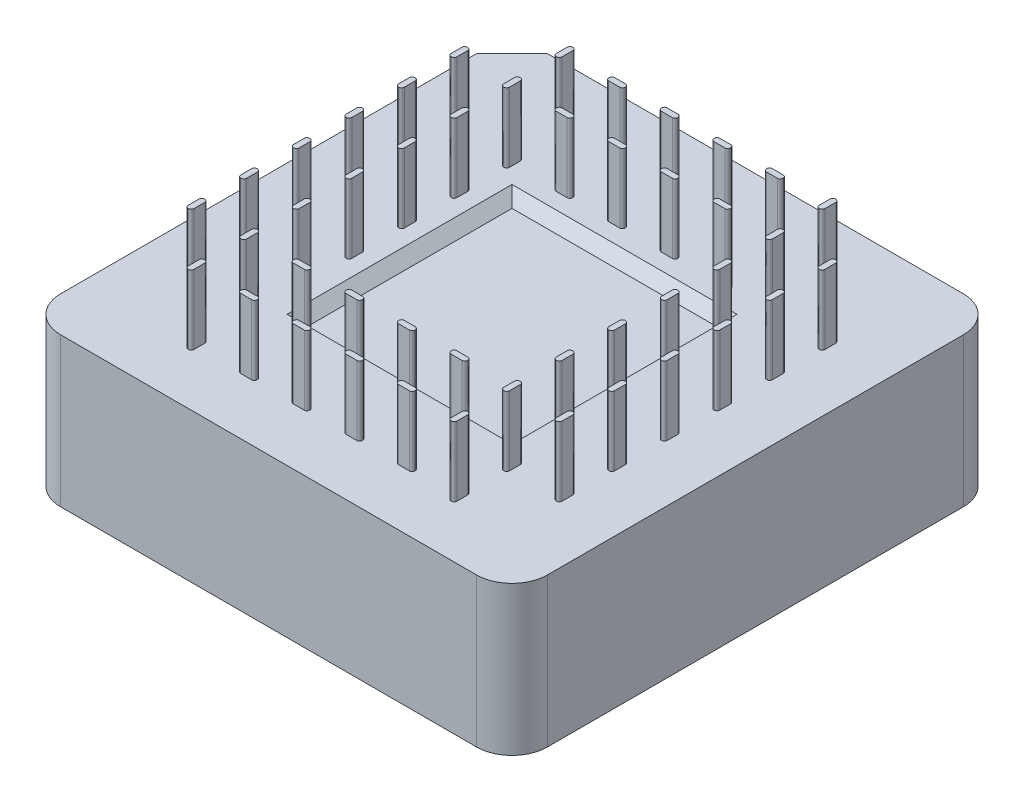
SolidWorks part; units mm, degrees
ref_plane "Alzado" through (0, 0, 0) normal (0, 0, 1) x (1, 0, 0)
ref_plane "pcb" through (0, 0, 0) normal (0, 1, 0) x (1, 0, 0)
ref_plane "Vista lateral" through (0, 0, 0) normal (1, 0, 0) x (0, 0, -1)
sketch "Croquis1" plane through (0, 0, 0) normal (0, 1, 0) x (1, 0, 0)
  line L0 (0, 0) -> (-6.35, 0) construction
  line L1 (-9.0297, -6.7437) -> (-8.7503, -5.9563) construction
  line L2 (-7.62, 0) -> (-8.89, 0) construction
  line L3 (-7.62, -7.62) -> (-7.62, -5.08) construction
  line L4 (-7.62, -7.62) -> (-8.89, -7.62) construction
  line L5 (-6.2103, -8.4963) -> (-6.4897, -9.2837) construction
  line L6 (-6.2103, -9.2837) -> (-6.4897, -8.4963) construction
  line L7 (-6.3432, -8.4963) -> (-6.3568, -8.4963)
  line L8 (-6.2103, -8.6292) -> (-6.2103, -9.1508)
  line L9 (-6.3432, -9.2837) -> (-6.3568, -9.2837)
  line L10 (-6.4897, -8.6292) -> (-6.4897, -9.1508)
  line L11 (-6.35, 6.35) -> (-7.62, 6.35) construction
  line L12 (-6.2103, 6.7437) -> (-6.4897, 5.9563) construction
  line L13 (-6.2103, 5.9563) -> (-6.4897, 6.7437) construction
  line L14 (-9.0297, 5.9563) -> (-8.7503, 6.7437) construction
  line L15 (-7.62, 5.08) -> (-8.89, 5.08) construction
  line L16 (-7.62, -2.54) -> (-8.89, -2.54) construction
  line L17 (-9.0297, -1.6637) -> (-8.7503, -0.8763) construction
  line L18 (-9.0297, -0.8763) -> (-8.7503, -1.6637) construction
  line L19 (-6.2103, -0.8763) -> (-6.4897, -1.6637) construction
  line L20 (-6.2103, -1.6637) -> (-6.4897, -0.8763) construction
  line L21 (-6.35, -1.27) -> (-7.62, -1.27) construction
  line L22 (-8.8968, -1.6637) -> (-8.8832, -1.6637)
  line L23 (-9.0297, -1.5308) -> (-9.0297, -1.0092)
  line L24 (-8.8968, -0.8763) -> (-8.8832, -0.8763)
  line L25 (-8.7503, -1.5308) -> (-8.7503, -1.0092)
  line L26 (-6.4897, -1.5308) -> (-6.4897, -1.0092)
  line L27 (-6.3432, -0.8763) -> (-6.3568, -0.8763)
  line L28 (-6.2103, -1.5308) -> (-6.2103, -1.0092)
  line L29 (-6.3432, -1.6637) -> (-6.3568, -1.6637)
  line L30 (-6.35, -3.81) -> (-7.62, -3.81) construction
  line L31 (-6.2103, -3.4163) -> (-6.4897, -4.2037) construction
  line L32 (-6.2103, -4.2037) -> (-6.4897, -3.4163) construction
  line L33 (-9.0297, -4.2037) -> (-8.7503, -3.4163) construction
  line L34 (-9.0297, -3.4163) -> (-8.7503, -4.2037) construction
  line L35 (-6.3432, -3.4163) -> (-6.3568, -3.4163)
  line L36 (-6.2103, -3.5492) -> (-6.2103, -4.0708)
  line L37 (-6.3432, -4.2037) -> (-6.3568, -4.2037)
  line L38 (-6.4897, -3.5492) -> (-6.4897, -4.0708)
  line L39 (-8.7503, -3.5492) -> (-8.7503, -4.0708)
  line L40 (-8.8968, -4.2037) -> (-8.8832, -4.2037)
  line L41 (-9.0297, -3.5492) -> (-9.0297, -4.0708)
  line L42 (-8.8968, -3.4163) -> (-8.8832, -3.4163)
  line L43 (-7.62, -5.08) -> (-8.89, -5.08) construction
  line L44 (-9.0297, -5.9563) -> (-8.7503, -6.7437) construction
  line L45 (-6.2103, -5.9563) -> (-6.4897, -6.7437) construction
  line L46 (-6.2103, -6.7437) -> (-6.4897, -5.9563) construction
  line L47 (-6.35, -6.35) -> (-7.62, -6.35) construction
  line L48 (-8.8968, -6.7437) -> (-8.8832, -6.7437)
  line L49 (-9.0297, -6.6108) -> (-9.0297, -6.0892)
  line L50 (-8.8968, -5.9563) -> (-8.8832, -5.9563)
  line L51 (-8.7503, -6.6108) -> (-8.7503, -6.0892)
  line L52 (-6.4897, -6.6108) -> (-6.4897, -6.0892)
  line L53 (-6.3432, -5.9563) -> (-6.3568, -5.9563)
  line L54 (-6.2103, -6.6108) -> (-6.2103, -6.0892)
  line L55 (-6.3432, -6.7437) -> (-6.3568, -6.7437)
  line L56 (-9.0297, 3.4163) -> (-8.7503, 4.2037) construction
  line L57 (-9.0297, 4.2037) -> (-8.7503, 3.4163) construction
  line L58 (-6.2103, 4.2037) -> (-6.4897, 3.4163) construction
  line L59 (-6.2103, 3.4163) -> (-6.4897, 4.2037) construction
  line L60 (-6.35, 3.81) -> (-7.62, 3.81) construction
  line L61 (-6.35, 1.27) -> (-7.62, 1.27) construction
  line L62 (-6.2103, 1.6637) -> (-6.4897, 0.8763) construction
  line L63 (-6.2103, 0.8763) -> (-6.4897, 1.6637) construction
  line L64 (-9.0297, 0.8763) -> (-8.7503, 1.6637) construction
  line L65 (-9.0297, 1.6637) -> (-8.7503, 0.8763) construction
  line L66 (-7.62, 2.54) -> (-8.89, 2.54) construction
  line L67 (-6.2103, 9.2837) -> (-6.4897, 8.4963) construction
  line L68 (-6.2103, 8.4963) -> (-6.4897, 9.2837) construction
  line L69 (-7.62, 7.62) -> (-8.89, 7.62) construction
  line L70 (-7.62, 7.62) -> (-7.62, 5.08) construction
  line L71 (-9.0297, 6.7437) -> (-8.7503, 5.9563) construction
  line L72 (-6.3432, 6.7437) -> (-6.3568, 6.7437)
  line L73 (-6.2103, 6.6108) -> (-6.2103, 6.0892)
  line L74 (-6.3432, 5.9563) -> (-6.3568, 5.9563)
  line L75 (-6.4897, 6.6108) -> (-6.4897, 6.0892)
  line L76 (-8.7503, 6.6108) -> (-8.7503, 6.0892)
  line L77 (-8.8968, 5.9563) -> (-8.8832, 5.9563)
  line L78 (-9.0297, 6.6108) -> (-9.0297, 6.0892)
  line L79 (-8.8968, 6.7437) -> (-8.8832, 6.7437)
  line L80 (-8.8968, 3.4163) -> (-8.8832, 3.4163)
  line L81 (-9.0297, 3.5492) -> (-9.0297, 4.0708)
  line L82 (-8.8968, 4.2037) -> (-8.8832, 4.2037)
  line L83 (-8.7503, 3.5492) -> (-8.7503, 4.0708)
  line L84 (-6.4897, 3.5492) -> (-6.4897, 4.0708)
  line L85 (-6.3432, 4.2037) -> (-6.3568, 4.2037)
  line L86 (-6.2103, 3.5492) -> (-6.2103, 4.0708)
  line L87 (-6.3432, 3.4163) -> (-6.3568, 3.4163)
  line L88 (-6.3432, 1.6637) -> (-6.3568, 1.6637)
  line L89 (-6.2103, 1.5308) -> (-6.2103, 1.0092)
  line L90 (-6.3432, 0.8763) -> (-6.3568, 0.8763)
  line L91 (-6.4897, 1.5308) -> (-6.4897, 1.0092)
  line L92 (-8.7503, 1.5308) -> (-8.7503, 1.0092)
  line L93 (-8.8968, 0.8763) -> (-8.8832, 0.8763)
  line L94 (-9.0297, 1.5308) -> (-9.0297, 1.0092)
  line L95 (-8.8968, 1.6637) -> (-8.8832, 1.6637)
  line L96 (-6.4897, 8.6292) -> (-6.4897, 9.1508)
  line L97 (-6.3432, 9.2837) -> (-6.3568, 9.2837)
  line L98 (-6.2103, 8.6292) -> (-6.2103, 9.1508)
  line L99 (-6.3432, 8.4963) -> (-6.3568, 8.4963)
  line L100 (9.0297, 6.7437) -> (8.7503, 5.9563) construction
  line L101 (7.62, 7.62) -> (7.62, 5.08) construction
  line L102 (7.62, 7.62) -> (8.89, 7.62) construction
  line L103 (6.2103, 8.4963) -> (6.4897, 9.2837) construction
  line L104 (6.2103, 9.2837) -> (6.4897, 8.4963) construction
  line L105 (7.62, 2.54) -> (8.89, 2.54) construction
  line L106 (9.0297, 1.6637) -> (8.7503, 0.8763) construction
  line L107 (9.0297, 0.8763) -> (8.7503, 1.6637) construction
  line L108 (6.2103, 0.8763) -> (6.4897, 1.6637) construction
  line L109 (6.2103, 1.6637) -> (6.4897, 0.8763) construction
  line L110 (6.35, 1.27) -> (7.62, 1.27) construction
  line L111 (6.35, 3.81) -> (7.62, 3.81) construction
  line L112 (6.2103, 3.4163) -> (6.4897, 4.2037) construction
  line L113 (6.2103, 4.2037) -> (6.4897, 3.4163) construction
  line L114 (9.0297, 4.2037) -> (8.7503, 3.4163) construction
  line L115 (9.0297, 3.4163) -> (8.7503, 4.2037) construction
  line L116 (6.35, -6.35) -> (7.62, -6.35) construction
  line L117 (6.2103, -6.7437) -> (6.4897, -5.9563) construction
  line L118 (6.2103, -5.9563) -> (6.4897, -6.7437) construction
  line L119 (9.0297, -5.9563) -> (8.7503, -6.7437) construction
  line L120 (7.62, -5.08) -> (8.89, -5.08) construction
  line L121 (9.0297, -3.4163) -> (8.7503, -4.2037) construction
  line L122 (9.0297, -4.2037) -> (8.7503, -3.4163) construction
  line L123 (6.2103, -4.2037) -> (6.4897, -3.4163) construction
  line L124 (6.2103, -3.4163) -> (6.4897, -4.2037) construction
  line L125 (6.35, -3.81) -> (7.62, -3.81) construction
  line L126 (6.35, -1.27) -> (7.62, -1.27) construction
  line L127 (6.2103, -1.6637) -> (6.4897, -0.8763) construction
  line L128 (6.2103, -0.8763) -> (6.4897, -1.6637) construction
  line L129 (9.0297, -0.8763) -> (8.7503, -1.6637) construction
  line L130 (9.0297, -1.6637) -> (8.7503, -0.8763) construction
  line L131 (7.62, -2.54) -> (8.89, -2.54) construction
  line L132 (7.62, 5.08) -> (8.89, 5.08) construction
  line L133 (9.0297, 5.9563) -> (8.7503, 6.7437) construction
  line L134 (6.2103, 5.9563) -> (6.4897, 6.7437) construction
  line L135 (6.2103, 6.7437) -> (6.4897, 5.9563) construction
  line L136 (6.35, 6.35) -> (7.62, 6.35) construction
  line L137 (6.2103, -9.2837) -> (6.4897, -8.4963) construction
  line L138 (6.2103, -8.4963) -> (6.4897, -9.2837) construction
  line L139 (7.62, -7.62) -> (8.89, -7.62) construction
  line L140 (7.62, -7.62) -> (7.62, -5.08) construction
  line L141 (7.62, 0) -> (8.89, 0) construction
  line L142 (9.0297, -6.7437) -> (8.7503, -5.9563) construction
  line L143 (6.3432, 8.4963) -> (6.3568, 8.4963)
  line L144 (6.2103, 8.6292) -> (6.2103, 9.1508)
  line L145 (6.3432, 9.2837) -> (6.3568, 9.2837)
  line L146 (6.4897, 8.6292) -> (6.4897, 9.1508)
  line L147 (8.8968, 1.6637) -> (8.8832, 1.6637)
  line L148 (9.0297, 1.5308) -> (9.0297, 1.0092)
  line L149 (8.8968, 0.8763) -> (8.8832, 0.8763)
  line L150 (8.7503, 1.5308) -> (8.7503, 1.0092)
  line L151 (6.4897, 1.5308) -> (6.4897, 1.0092)
  line L152 (6.3432, 0.8763) -> (6.3568, 0.8763)
  line L153 (6.2103, 1.5308) -> (6.2103, 1.0092)
  line L154 (6.3432, 1.6637) -> (6.3568, 1.6637)
  line L155 (6.3432, 3.4163) -> (6.3568, 3.4163)
  line L156 (6.2103, 3.5492) -> (6.2103, 4.0708)
  line L157 (0, 6.35) -> (0, -6.35) construction
  line L158 (6.3432, 4.2037) -> (6.3568, 4.2037)
  line L159 (6.4897, 3.5492) -> (6.4897, 4.0708)
  line L160 (8.7503, 3.5492) -> (8.7503, 4.0708)
  line L161 (8.8968, 4.2037) -> (8.8832, 4.2037)
  line L162 (9.0297, 3.5492) -> (9.0297, 4.0708)
  line L163 (8.8968, 3.4163) -> (8.8832, 3.4163)
  line L164 (8.8968, 6.7437) -> (8.8832, 6.7437)
  line L165 (9.0297, 6.6108) -> (9.0297, 6.0892)
  line L166 (8.8968, 5.9563) -> (8.8832, 5.9563)
  line L167 (8.7503, 6.6108) -> (8.7503, 6.0892)
  line L168 (6.4897, 6.6108) -> (6.4897, 6.0892)
  line L169 (6.3432, 5.9563) -> (6.3568, 5.9563)
  line L170 (6.2103, 6.6108) -> (6.2103, 6.0892)
  line L171 (6.3432, 6.7437) -> (6.3568, 6.7437)
  line L172 (6.3432, -6.7437) -> (6.3568, -6.7437)
  line L173 (6.2103, -6.6108) -> (6.2103, -6.0892)
  line L174 (6.3432, -5.9563) -> (6.3568, -5.9563)
  line L175 (6.4897, -6.6108) -> (6.4897, -6.0892)
  line L176 (8.7503, -6.6108) -> (8.7503, -6.0892)
  line L177 (8.8968, -5.9563) -> (8.8832, -5.9563)
  line L178 (9.0297, -6.6108) -> (9.0297, -6.0892)
  line L179 (8.8968, -6.7437) -> (8.8832, -6.7437)
  line L180 (8.8968, -3.4163) -> (8.8832, -3.4163)
  line L181 (9.0297, -3.5492) -> (9.0297, -4.0708)
  line L182 (8.8968, -4.2037) -> (8.8832, -4.2037)
  line L183 (8.7503, -3.5492) -> (8.7503, -4.0708)
  line L184 (6.4897, -3.5492) -> (6.4897, -4.0708)
  line L185 (6.3432, -4.2037) -> (6.3568, -4.2037)
  line L186 (6.2103, -3.5492) -> (6.2103, -4.0708)
  line L187 (6.3432, -3.4163) -> (6.3568, -3.4163)
  line L188 (6.3432, -1.6637) -> (6.3568, -1.6637)
  line L189 (6.2103, -1.5308) -> (6.2103, -1.0092)
  line L190 (6.3432, -0.8763) -> (6.3568, -0.8763)
  line L191 (6.4897, -1.5308) -> (6.4897, -1.0092)
  line L192 (8.7503, -1.5308) -> (8.7503, -1.0092)
  line L193 (8.8968, -0.8763) -> (8.8832, -0.8763)
  line L194 (9.0297, -1.5308) -> (9.0297, -1.0092)
  line L195 (8.8968, -1.6637) -> (8.8832, -1.6637)
  line L196 (6.4897, -8.6292) -> (6.4897, -9.1508)
  line L197 (6.3432, -9.2837) -> (6.3568, -9.2837)
  line L198 (6.2103, -8.6292) -> (6.2103, -9.1508)
  line L199 (6.3432, -8.4963) -> (6.3568, -8.4963)
  line L200 (-6.35, -6.35) -> (-5.08, -6.35) construction
  line L201 (-5.08, -6.35) -> (-5.08, -5.08) construction
  line L202 (-5.08, -6.35) -> (-3.81, -6.35) construction
  line L203 (-3.81, -6.35) -> (-2.54, -6.35) construction
  line L204 (-3.5426, -6.2103) -> (-4.0774, -6.2103)
  line L205 (-3.4163, -6.3366) -> (-3.4163, -6.3634)
  line L206 (-3.5426, -6.4897) -> (-4.0774, -6.4897)
  line L207 (-4.2037, -6.3366) -> (-4.2037, -6.3634)
  line L208 (-3.4163, -6.2103) -> (-4.2037, -6.4897) construction
  line L209 (-3.4163, -6.4897) -> (-4.2037, -6.2103) construction
  line L210 (-2.54, -6.35) -> (-2.54, -5.08) construction
  line L211 (-1.6637, -6.4897) -> (-0.8763, -6.2103) construction
  line L212 (-1.6637, -6.2103) -> (-0.8763, -6.4897) construction
  line L213 (-0.8763, -6.3366) -> (-0.8763, -6.3634)
  line L214 (-1.5374, -6.4897) -> (-1.0026, -6.4897)
  line L215 (-1.6637, -6.3366) -> (-1.6637, -6.3634)
  line L216 (-1.5374, -6.2103) -> (-1.0026, -6.2103)
  line L217 (1.6637, -6.2103) -> (0.8763, -6.4897) construction
  line L218 (1.6637, -6.4897) -> (0.8763, -6.2103) construction
  line L219 (3.4163, -6.4897) -> (4.2037, -6.2103) construction
  line L220 (3.4163, -6.2103) -> (4.2037, -6.4897) construction
  line L221 (3.81, -6.35) -> (2.54, -6.35) construction
  line L222 (1.5374, -6.2103) -> (1.0026, -6.2103)
  line L223 (1.6637, -6.3366) -> (1.6637, -6.3634)
  line L224 (1.5374, -6.4897) -> (1.0026, -6.4897)
  line L225 (0.8763, -6.3366) -> (0.8763, -6.3634)
  line L226 (4.2037, -6.3366) -> (4.2037, -6.3634)
  line L227 (3.5426, -6.4897) -> (4.0774, -6.4897)
  line L228 (3.4163, -6.3366) -> (3.4163, -6.3634)
  line L229 (3.5426, -6.2103) -> (4.0774, -6.2103)
  line L230 (-2.54, -6.35) -> (-2.54, -7.62) construction
  line L231 (-2.54, -7.62) -> (-3.81, -7.62) construction
  line L232 (3.81, -8.89) -> (2.54, -8.89) construction
  line L233 (3.4163, -9.0297) -> (4.2037, -8.7503) construction
  line L234 (3.4163, -8.7503) -> (4.2037, -9.0297) construction
  line L235 (1.6637, -8.7503) -> (0.8763, -9.0297) construction
  line L236 (1.6637, -9.0297) -> (0.8763, -8.7503) construction
  line L237 (-1.6637, -9.0297) -> (-0.8763, -8.7503) construction
  line L238 (-1.6637, -8.7503) -> (-0.8763, -9.0297) construction
  line L239 (-3.4163, -8.7503) -> (-4.2037, -9.0297) construction
  line L240 (-3.4163, -9.0297) -> (-4.2037, -8.7503) construction
  line L241 (-3.81, -8.89) -> (-2.54, -8.89) construction
  line L242 (3.5426, -9.0297) -> (4.0774, -9.0297)
  line L243 (3.4163, -8.9034) -> (3.4163, -8.8766)
  line L244 (3.5426, -8.7503) -> (4.0774, -8.7503)
  line L245 (4.2037, -8.9034) -> (4.2037, -8.8766)
  line L246 (0.8763, -8.9034) -> (0.8763, -8.8766)
  line L247 (1.5374, -8.7503) -> (1.0026, -8.7503)
  line L248 (1.6637, -8.9034) -> (1.6637, -8.8766)
  line L249 (1.5374, -9.0297) -> (1.0026, -9.0297)
  line L250 (-1.5374, -9.0297) -> (-1.0026, -9.0297)
  line L251 (-1.6637, -8.9034) -> (-1.6637, -8.8766)
  line L252 (-1.5374, -8.7503) -> (-1.0026, -8.7503)
  line L253 (-0.8763, -8.9034) -> (-0.8763, -8.8766)
  line L254 (-4.2037, -8.9034) -> (-4.2037, -8.8766)
  line L255 (-3.5426, -8.7503) -> (-4.0774, -8.7503)
  line L256 (-3.4163, -8.9034) -> (-3.4163, -8.8766)
  line L257 (-3.5426, -9.0297) -> (-4.0774, -9.0297)
  line L258 (-3.81, 8.89) -> (-2.54, 8.89) construction
  line L259 (-3.4163, 9.0297) -> (-4.2037, 8.7503) construction
  line L260 (-3.4163, 8.7503) -> (-4.2037, 9.0297) construction
  line L261 (-1.6637, 8.7503) -> (-0.8763, 9.0297) construction
  line L262 (-1.6637, 9.0297) -> (-0.8763, 8.7503) construction
  line L263 (1.6637, 9.0297) -> (0.8763, 8.7503) construction
  line L264 (1.6637, 8.7503) -> (0.8763, 9.0297) construction
  line L265 (3.4163, 8.7503) -> (4.2037, 9.0297) construction
  line L266 (3.4163, 9.0297) -> (4.2037, 8.7503) construction
  line L267 (3.81, 8.89) -> (2.54, 8.89) construction
  line L268 (-2.54, 7.62) -> (-3.81, 7.62) construction
  line L269 (-2.54, 6.35) -> (-2.54, 7.62) construction
  line L270 (3.81, 6.35) -> (2.54, 6.35) construction
  line L271 (3.4163, 6.2103) -> (4.2037, 6.4897) construction
  line L272 (3.4163, 6.4897) -> (4.2037, 6.2103) construction
  line L273 (1.6637, 6.4897) -> (0.8763, 6.2103) construction
  line L274 (1.6637, 6.2103) -> (0.8763, 6.4897) construction
  line L275 (-1.6637, 6.2103) -> (-0.8763, 6.4897) construction
  line L276 (-1.6637, 6.4897) -> (-0.8763, 6.2103) construction
  line L277 (-2.54, 6.35) -> (-2.54, 5.08) construction
  line L278 (-3.4163, 6.4897) -> (-4.2037, 6.2103) construction
  line L279 (-3.4163, 6.2103) -> (-4.2037, 6.4897) construction
  line L280 (-3.81, 6.35) -> (-2.54, 6.35) construction
  line L281 (-5.08, 6.35) -> (-3.81, 6.35) construction
  line L282 (-3.5426, 9.0297) -> (-4.0774, 9.0297)
  line L283 (-3.4163, 8.9034) -> (-3.4163, 8.8766)
  line L284 (-3.5426, 8.7503) -> (-4.0774, 8.7503)
  line L285 (-4.2037, 8.9034) -> (-4.2037, 8.8766)
  line L286 (-0.8763, 8.9034) -> (-0.8763, 8.8766)
  line L287 (-1.5374, 8.7503) -> (-1.0026, 8.7503)
  line L288 (-1.6637, 8.9034) -> (-1.6637, 8.8766)
  line L289 (-1.5374, 9.0297) -> (-1.0026, 9.0297)
  line L290 (1.5374, 9.0297) -> (1.0026, 9.0297)
  line L291 (1.6637, 8.9034) -> (1.6637, 8.8766)
  line L292 (1.5374, 8.7503) -> (1.0026, 8.7503)
  line L293 (0.8763, 8.9034) -> (0.8763, 8.8766)
  line L294 (4.2037, 8.9034) -> (4.2037, 8.8766)
  line L295 (3.5426, 8.7503) -> (4.0774, 8.7503)
  line L296 (3.4163, 8.9034) -> (3.4163, 8.8766)
  line L297 (3.5426, 9.0297) -> (4.0774, 9.0297)
  line L298 (3.5426, 6.2103) -> (4.0774, 6.2103)
  line L299 (3.4163, 6.3366) -> (3.4163, 6.3634)
  line L300 (3.5426, 6.4897) -> (4.0774, 6.4897)
  line L301 (4.2037, 6.3366) -> (4.2037, 6.3634)
  line L302 (0.8763, 6.3366) -> (0.8763, 6.3634)
  line L303 (1.5374, 6.4897) -> (1.0026, 6.4897)
  line L304 (1.6637, 6.3366) -> (1.6637, 6.3634)
  line L305 (1.5374, 6.2103) -> (1.0026, 6.2103)
  line L306 (-1.5374, 6.2103) -> (-1.0026, 6.2103)
  line L307 (-1.6637, 6.3366) -> (-1.6637, 6.3634)
  line L308 (-1.5374, 6.4897) -> (-1.0026, 6.4897)
  line L309 (-0.8763, 6.3366) -> (-0.8763, 6.3634)
  line L310 (-4.2037, 6.3366) -> (-4.2037, 6.3634)
  line L311 (-3.5426, 6.4897) -> (-4.0774, 6.4897)
  line L312 (-3.4163, 6.3366) -> (-3.4163, 6.3634)
  line L313 (-3.5426, 6.2103) -> (-4.0774, 6.2103)
  arc A0 (-6.3432, -9.2837) -> (-6.2103, -9.1508) centre (-6.3432, -9.1508) ccw
  arc A1 (-6.3568, -9.2837) -> (-6.4897, -9.1508) centre (-6.3568, -9.1508) cw
  arc A2 (-6.2103, -8.6292) -> (-6.3432, -8.4963) centre (-6.3432, -8.6292) ccw
  arc A3 (-6.3568, -8.4963) -> (-6.4897, -8.6292) centre (-6.3568, -8.6292) ccw
  arc A4 (-6.3432, 5.9563) -> (-6.2103, 6.0892) centre (-6.3432, 6.0892) ccw
  arc A5 (-6.3568, 5.9563) -> (-6.4897, 6.0892) centre (-6.3568, 6.0892) cw
  arc A6 (-6.2103, 6.6108) -> (-6.3432, 6.7437) centre (-6.3432, 6.6108) ccw
  arc A7 (-6.3568, 6.7437) -> (-6.4897, 6.6108) centre (-6.3568, 6.6108) ccw
  arc A8 (-8.8968, -0.8763) -> (-9.0297, -1.0092) centre (-8.8968, -1.0092) ccw
  arc A9 (-8.8832, -0.8763) -> (-8.7503, -1.0092) centre (-8.8832, -1.0092) cw
  arc A10 (-9.0297, -1.5308) -> (-8.8968, -1.6637) centre (-8.8968, -1.5308) ccw
  arc A11 (-8.8832, -1.6637) -> (-8.7503, -1.5308) centre (-8.8832, -1.5308) ccw
  arc A12 (-6.3568, -1.6637) -> (-6.4897, -1.5308) centre (-6.3568, -1.5308) cw
  arc A13 (-6.2103, -1.5308) -> (-6.3432, -1.6637) centre (-6.3432, -1.5308) cw
  arc A14 (-6.3568, -0.8763) -> (-6.4897, -1.0092) centre (-6.3568, -1.0092) ccw
  arc A15 (-6.3432, -0.8763) -> (-6.2103, -1.0092) centre (-6.3432, -1.0092) cw
  arc A16 (-6.3432, -4.2037) -> (-6.2103, -4.0708) centre (-6.3432, -4.0708) ccw
  arc A17 (-6.3568, -4.2037) -> (-6.4897, -4.0708) centre (-6.3568, -4.0708) cw
  arc A18 (-6.2103, -3.5492) -> (-6.3432, -3.4163) centre (-6.3432, -3.5492) ccw
  arc A19 (-6.3568, -3.4163) -> (-6.4897, -3.5492) centre (-6.3568, -3.5492) ccw
  arc A20 (-8.8832, -3.4163) -> (-8.7503, -3.5492) centre (-8.8832, -3.5492) cw
  arc A21 (-9.0297, -3.5492) -> (-8.8968, -3.4163) centre (-8.8968, -3.5492) cw
  arc A22 (-8.8832, -4.2037) -> (-8.7503, -4.0708) centre (-8.8832, -4.0708) ccw
  arc A23 (-8.8968, -4.2037) -> (-9.0297, -4.0708) centre (-8.8968, -4.0708) cw
  arc A24 (-8.8968, -5.9563) -> (-9.0297, -6.0892) centre (-8.8968, -6.0892) ccw
  arc A25 (-8.8832, -5.9563) -> (-8.7503, -6.0892) centre (-8.8832, -6.0892) cw
  arc A26 (-9.0297, -6.6108) -> (-8.8968, -6.7437) centre (-8.8968, -6.6108) ccw
  arc A27 (-8.8832, -6.7437) -> (-8.7503, -6.6108) centre (-8.8832, -6.6108) ccw
  arc A28 (-6.3568, -6.7437) -> (-6.4897, -6.6108) centre (-6.3568, -6.6108) cw
  arc A29 (-6.2103, -6.6108) -> (-6.3432, -6.7437) centre (-6.3432, -6.6108) cw
  arc A30 (-6.3568, -5.9563) -> (-6.4897, -6.0892) centre (-6.3568, -6.0892) ccw
  arc A31 (-6.3432, -5.9563) -> (-6.2103, -6.0892) centre (-6.3432, -6.0892) cw
  arc A32 (-8.8832, 6.7437) -> (-8.7503, 6.6108) centre (-8.8832, 6.6108) cw
  arc A33 (-9.0297, 6.6108) -> (-8.8968, 6.7437) centre (-8.8968, 6.6108) cw
  arc A34 (-8.8832, 5.9563) -> (-8.7503, 6.0892) centre (-8.8832, 6.0892) ccw
  arc A35 (-8.8968, 5.9563) -> (-9.0297, 6.0892) centre (-8.8968, 6.0892) cw
  arc A36 (-8.8968, 4.2037) -> (-9.0297, 4.0708) centre (-8.8968, 4.0708) ccw
  arc A37 (-8.8832, 4.2037) -> (-8.7503, 4.0708) centre (-8.8832, 4.0708) cw
  arc A38 (-9.0297, 3.5492) -> (-8.8968, 3.4163) centre (-8.8968, 3.5492) ccw
  arc A39 (-8.8832, 3.4163) -> (-8.7503, 3.5492) centre (-8.8832, 3.5492) ccw
  arc A40 (-6.3568, 3.4163) -> (-6.4897, 3.5492) centre (-6.3568, 3.5492) cw
  arc A41 (-6.2103, 3.5492) -> (-6.3432, 3.4163) centre (-6.3432, 3.5492) cw
  arc A42 (-6.3568, 4.2037) -> (-6.4897, 4.0708) centre (-6.3568, 4.0708) ccw
  arc A43 (-6.3432, 4.2037) -> (-6.2103, 4.0708) centre (-6.3432, 4.0708) cw
  arc A44 (-6.3432, 0.8763) -> (-6.2103, 1.0092) centre (-6.3432, 1.0092) ccw
  arc A45 (-6.3568, 0.8763) -> (-6.4897, 1.0092) centre (-6.3568, 1.0092) cw
  arc A46 (-6.2103, 1.5308) -> (-6.3432, 1.6637) centre (-6.3432, 1.5308) ccw
  arc A47 (-6.3568, 1.6637) -> (-6.4897, 1.5308) centre (-6.3568, 1.5308) ccw
  arc A48 (-8.8832, 1.6637) -> (-8.7503, 1.5308) centre (-8.8832, 1.5308) cw
  arc A49 (-9.0297, 1.5308) -> (-8.8968, 1.6637) centre (-8.8968, 1.5308) cw
  arc A50 (-8.8832, 0.8763) -> (-8.7503, 1.0092) centre (-8.8832, 1.0092) ccw
  arc A51 (-8.8968, 0.8763) -> (-9.0297, 1.0092) centre (-8.8968, 1.0092) cw
  arc A52 (-6.3568, 8.4963) -> (-6.4897, 8.6292) centre (-6.3568, 8.6292) cw
  arc A53 (-6.2103, 8.6292) -> (-6.3432, 8.4963) centre (-6.3432, 8.6292) cw
  arc A54 (-6.3568, 9.2837) -> (-6.4897, 9.1508) centre (-6.3568, 9.1508) ccw
  arc A55 (-6.3432, 9.2837) -> (-6.2103, 9.1508) centre (-6.3432, 9.1508) cw
  arc A56 (6.3432, 9.2837) -> (6.2103, 9.1508) centre (6.3432, 9.1508) ccw
  arc A57 (6.3568, 9.2837) -> (6.4897, 9.1508) centre (6.3568, 9.1508) cw
  arc A58 (6.2103, 8.6292) -> (6.3432, 8.4963) centre (6.3432, 8.6292) ccw
  arc A59 (6.3568, 8.4963) -> (6.4897, 8.6292) centre (6.3568, 8.6292) ccw
  arc A60 (8.8968, 0.8763) -> (9.0297, 1.0092) centre (8.8968, 1.0092) ccw
  arc A61 (8.8832, 0.8763) -> (8.7503, 1.0092) centre (8.8832, 1.0092) cw
  arc A62 (9.0297, 1.5308) -> (8.8968, 1.6637) centre (8.8968, 1.5308) ccw
  arc A63 (8.8832, 1.6637) -> (8.7503, 1.5308) centre (8.8832, 1.5308) ccw
  arc A64 (6.3568, 1.6637) -> (6.4897, 1.5308) centre (6.3568, 1.5308) cw
  arc A65 (6.2103, 1.5308) -> (6.3432, 1.6637) centre (6.3432, 1.5308) cw
  arc A66 (6.3568, 0.8763) -> (6.4897, 1.0092) centre (6.3568, 1.0092) ccw
  arc A67 (6.3432, 0.8763) -> (6.2103, 1.0092) centre (6.3432, 1.0092) cw
  arc A68 (6.3432, 4.2037) -> (6.2103, 4.0708) centre (6.3432, 4.0708) ccw
  arc A69 (6.3568, 4.2037) -> (6.4897, 4.0708) centre (6.3568, 4.0708) cw
  arc A70 (6.2103, 3.5492) -> (6.3432, 3.4163) centre (6.3432, 3.5492) ccw
  arc A71 (6.3568, 3.4163) -> (6.4897, 3.5492) centre (6.3568, 3.5492) ccw
  arc A72 (8.8832, 3.4163) -> (8.7503, 3.5492) centre (8.8832, 3.5492) cw
  arc A73 (9.0297, 3.5492) -> (8.8968, 3.4163) centre (8.8968, 3.5492) cw
  arc A74 (8.8832, 4.2037) -> (8.7503, 4.0708) centre (8.8832, 4.0708) ccw
  arc A75 (8.8968, 4.2037) -> (9.0297, 4.0708) centre (8.8968, 4.0708) cw
  arc A76 (8.8968, 5.9563) -> (9.0297, 6.0892) centre (8.8968, 6.0892) ccw
  arc A77 (8.8832, 5.9563) -> (8.7503, 6.0892) centre (8.8832, 6.0892) cw
  arc A78 (9.0297, 6.6108) -> (8.8968, 6.7437) centre (8.8968, 6.6108) ccw
  arc A79 (8.8832, 6.7437) -> (8.7503, 6.6108) centre (8.8832, 6.6108) ccw
  arc A80 (6.3432, -5.9563) -> (6.2103, -6.0892) centre (6.3432, -6.0892) ccw
  arc A81 (6.3568, -5.9563) -> (6.4897, -6.0892) centre (6.3568, -6.0892) cw
  arc A82 (6.2103, -6.6108) -> (6.3432, -6.7437) centre (6.3432, -6.6108) ccw
  arc A83 (6.3568, -6.7437) -> (6.4897, -6.6108) centre (6.3568, -6.6108) ccw
  arc A84 (8.8832, -6.7437) -> (8.7503, -6.6108) centre (8.8832, -6.6108) cw
  arc A85 (9.0297, -6.6108) -> (8.8968, -6.7437) centre (8.8968, -6.6108) cw
  arc A86 (8.8832, -5.9563) -> (8.7503, -6.0892) centre (8.8832, -6.0892) ccw
  arc A87 (8.8968, -5.9563) -> (9.0297, -6.0892) centre (8.8968, -6.0892) cw
  arc A88 (8.8968, -4.2037) -> (9.0297, -4.0708) centre (8.8968, -4.0708) ccw
  arc A89 (8.8832, -4.2037) -> (8.7503, -4.0708) centre (8.8832, -4.0708) cw
  arc A90 (9.0297, -3.5492) -> (8.8968, -3.4163) centre (8.8968, -3.5492) ccw
  arc A91 (8.8832, -3.4163) -> (8.7503, -3.5492) centre (8.8832, -3.5492) ccw
  arc A92 (6.3568, -3.4163) -> (6.4897, -3.5492) centre (6.3568, -3.5492) cw
  arc A93 (6.2103, -3.5492) -> (6.3432, -3.4163) centre (6.3432, -3.5492) cw
  arc A94 (6.3568, -4.2037) -> (6.4897, -4.0708) centre (6.3568, -4.0708) ccw
  arc A95 (6.3432, -4.2037) -> (6.2103, -4.0708) centre (6.3432, -4.0708) cw
  arc A96 (6.3432, -0.8763) -> (6.2103, -1.0092) centre (6.3432, -1.0092) ccw
  arc A97 (6.3568, -0.8763) -> (6.4897, -1.0092) centre (6.3568, -1.0092) cw
  arc A98 (6.2103, -1.5308) -> (6.3432, -1.6637) centre (6.3432, -1.5308) ccw
  arc A99 (6.3568, -1.6637) -> (6.4897, -1.5308) centre (6.3568, -1.5308) ccw
  arc A100 (8.8832, -1.6637) -> (8.7503, -1.5308) centre (8.8832, -1.5308) cw
  arc A101 (9.0297, -1.5308) -> (8.8968, -1.6637) centre (8.8968, -1.5308) cw
  arc A102 (8.8832, -0.8763) -> (8.7503, -1.0092) centre (8.8832, -1.0092) ccw
  arc A103 (8.8968, -0.8763) -> (9.0297, -1.0092) centre (8.8968, -1.0092) cw
  arc A104 (6.3568, 6.7437) -> (6.4897, 6.6108) centre (6.3568, 6.6108) cw
  arc A105 (6.2103, 6.6108) -> (6.3432, 6.7437) centre (6.3432, 6.6108) cw
  arc A106 (6.3568, 5.9563) -> (6.4897, 6.0892) centre (6.3568, 6.0892) ccw
  arc A107 (6.3432, 5.9563) -> (6.2103, 6.0892) centre (6.3432, 6.0892) cw
  arc A108 (6.3568, -8.4963) -> (6.4897, -8.6292) centre (6.3568, -8.6292) cw
  arc A109 (6.2103, -8.6292) -> (6.3432, -8.4963) centre (6.3432, -8.6292) cw
  arc A110 (6.3568, -9.2837) -> (6.4897, -9.1508) centre (6.3568, -9.1508) ccw
  arc A111 (6.3432, -9.2837) -> (6.2103, -9.1508) centre (6.3432, -9.1508) cw
  arc A112 (-3.5426, -6.4897) -> (-3.4163, -6.3634) centre (-3.5426, -6.3634) ccw
  arc A113 (-3.4163, -6.3366) -> (-3.5426, -6.2103) centre (-3.5426, -6.3366) ccw
  arc A114 (-4.0774, -6.4897) -> (-4.2037, -6.3634) centre (-4.0774, -6.3634) cw
  arc A115 (-4.0774, -6.2103) -> (-4.2037, -6.3366) centre (-4.0774, -6.3366) ccw
  arc A116 (-1.0026, -6.2103) -> (-0.8763, -6.3366) centre (-1.0026, -6.3366) cw
  arc A117 (-1.0026, -6.4897) -> (-0.8763, -6.3634) centre (-1.0026, -6.3634) ccw
  arc A118 (-1.6637, -6.3366) -> (-1.5374, -6.2103) centre (-1.5374, -6.3366) cw
  arc A119 (-1.5374, -6.4897) -> (-1.6637, -6.3634) centre (-1.5374, -6.3634) cw
  arc A120 (1.5374, -6.4897) -> (1.6637, -6.3634) centre (1.5374, -6.3634) ccw
  arc A121 (1.6637, -6.3366) -> (1.5374, -6.2103) centre (1.5374, -6.3366) ccw
  arc A122 (1.0026, -6.4897) -> (0.8763, -6.3634) centre (1.0026, -6.3634) cw
  arc A123 (1.0026, -6.2103) -> (0.8763, -6.3366) centre (1.0026, -6.3366) ccw
  arc A124 (4.0774, -6.2103) -> (4.2037, -6.3366) centre (4.0774, -6.3366) cw
  arc A125 (4.0774, -6.4897) -> (4.2037, -6.3634) centre (4.0774, -6.3634) ccw
  arc A126 (3.4163, -6.3366) -> (3.5426, -6.2103) centre (3.5426, -6.3366) cw
  arc A127 (3.5426, -6.4897) -> (3.4163, -6.3634) centre (3.5426, -6.3634) cw
  arc A128 (3.5426, -8.7503) -> (3.4163, -8.8766) centre (3.5426, -8.8766) ccw
  arc A129 (3.4163, -8.9034) -> (3.5426, -9.0297) centre (3.5426, -8.9034) ccw
  arc A130 (4.0774, -8.7503) -> (4.2037, -8.8766) centre (4.0774, -8.8766) cw
  arc A131 (4.0774, -9.0297) -> (4.2037, -8.9034) centre (4.0774, -8.9034) ccw
  arc A132 (1.0026, -9.0297) -> (0.8763, -8.9034) centre (1.0026, -8.9034) cw
  arc A133 (1.0026, -8.7503) -> (0.8763, -8.8766) centre (1.0026, -8.8766) ccw
  arc A134 (1.6637, -8.9034) -> (1.5374, -9.0297) centre (1.5374, -8.9034) cw
  arc A135 (1.5374, -8.7503) -> (1.6637, -8.8766) centre (1.5374, -8.8766) cw
  arc A136 (-1.5374, -8.7503) -> (-1.6637, -8.8766) centre (-1.5374, -8.8766) ccw
  arc A137 (-1.6637, -8.9034) -> (-1.5374, -9.0297) centre (-1.5374, -8.9034) ccw
  arc A138 (-1.0026, -8.7503) -> (-0.8763, -8.8766) centre (-1.0026, -8.8766) cw
  arc A139 (-1.0026, -9.0297) -> (-0.8763, -8.9034) centre (-1.0026, -8.9034) ccw
  arc A140 (-4.0774, -9.0297) -> (-4.2037, -8.9034) centre (-4.0774, -8.9034) cw
  arc A141 (-4.0774, -8.7503) -> (-4.2037, -8.8766) centre (-4.0774, -8.8766) ccw
  arc A142 (-3.4163, -8.9034) -> (-3.5426, -9.0297) centre (-3.5426, -8.9034) cw
  arc A143 (-3.5426, -8.7503) -> (-3.4163, -8.8766) centre (-3.5426, -8.8766) cw
  arc A144 (-3.5426, 8.7503) -> (-3.4163, 8.8766) centre (-3.5426, 8.8766) ccw
  arc A145 (-3.4163, 8.9034) -> (-3.5426, 9.0297) centre (-3.5426, 8.9034) ccw
  arc A146 (-4.0774, 8.7503) -> (-4.2037, 8.8766) centre (-4.0774, 8.8766) cw
  arc A147 (-4.0774, 9.0297) -> (-4.2037, 8.9034) centre (-4.0774, 8.9034) ccw
  arc A148 (-1.0026, 9.0297) -> (-0.8763, 8.9034) centre (-1.0026, 8.9034) cw
  arc A149 (-1.0026, 8.7503) -> (-0.8763, 8.8766) centre (-1.0026, 8.8766) ccw
  arc A150 (-1.6637, 8.9034) -> (-1.5374, 9.0297) centre (-1.5374, 8.9034) cw
  arc A151 (-1.5374, 8.7503) -> (-1.6637, 8.8766) centre (-1.5374, 8.8766) cw
  arc A152 (1.5374, 8.7503) -> (1.6637, 8.8766) centre (1.5374, 8.8766) ccw
  arc A153 (1.6637, 8.9034) -> (1.5374, 9.0297) centre (1.5374, 8.9034) ccw
  arc A154 (1.0026, 8.7503) -> (0.8763, 8.8766) centre (1.0026, 8.8766) cw
  arc A155 (1.0026, 9.0297) -> (0.8763, 8.9034) centre (1.0026, 8.9034) ccw
  arc A156 (4.0774, 9.0297) -> (4.2037, 8.9034) centre (4.0774, 8.9034) cw
  arc A157 (4.0774, 8.7503) -> (4.2037, 8.8766) centre (4.0774, 8.8766) ccw
  arc A158 (3.4163, 8.9034) -> (3.5426, 9.0297) centre (3.5426, 8.9034) cw
  arc A159 (3.5426, 8.7503) -> (3.4163, 8.8766) centre (3.5426, 8.8766) cw
  arc A160 (3.5426, 6.4897) -> (3.4163, 6.3634) centre (3.5426, 6.3634) ccw
  arc A161 (3.4163, 6.3366) -> (3.5426, 6.2103) centre (3.5426, 6.3366) ccw
  arc A162 (4.0774, 6.4897) -> (4.2037, 6.3634) centre (4.0774, 6.3634) cw
  arc A163 (4.0774, 6.2103) -> (4.2037, 6.3366) centre (4.0774, 6.3366) ccw
  arc A164 (1.0026, 6.2103) -> (0.8763, 6.3366) centre (1.0026, 6.3366) cw
  arc A165 (1.0026, 6.4897) -> (0.8763, 6.3634) centre (1.0026, 6.3634) ccw
  arc A166 (1.6637, 6.3366) -> (1.5374, 6.2103) centre (1.5374, 6.3366) cw
  arc A167 (1.5374, 6.4897) -> (1.6637, 6.3634) centre (1.5374, 6.3634) cw
  arc A168 (-1.5374, 6.4897) -> (-1.6637, 6.3634) centre (-1.5374, 6.3634) ccw
  arc A169 (-1.6637, 6.3366) -> (-1.5374, 6.2103) centre (-1.5374, 6.3366) ccw
  arc A170 (-1.0026, 6.4897) -> (-0.8763, 6.3634) centre (-1.0026, 6.3634) cw
  arc A171 (-1.0026, 6.2103) -> (-0.8763, 6.3366) centre (-1.0026, 6.3366) ccw
  arc A172 (-4.0774, 6.2103) -> (-4.2037, 6.3366) centre (-4.0774, 6.3366) cw
  arc A173 (-4.0774, 6.4897) -> (-4.2037, 6.3634) centre (-4.0774, 6.3634) ccw
  arc A174 (-3.4163, 6.3366) -> (-3.5426, 6.2103) centre (-3.5426, 6.3366) cw
  arc A175 (-3.5426, 6.4897) -> (-3.4163, 6.3634) centre (-3.5426, 6.3634) cw
  dimension "D4" = 1.27
  dimension "D9" = 0.1263
  dimension "D2" = 1.27
  dimension "D3" = 1.27
  dimension "D5" = 1.27
  dimension "D6" = 1.27
  dimension "D7" = 0.2794
  dimension "D8" = 0.7874
  dimension "D10" = 6.35
  dimension "D11" = 1.27
  dimension "D12" = 1.27
  dimension "D13" = 1.27
  dimension "D14" = 1.27
extrude "Saliente-Extruir1" add sketch "Croquis1" along normal blind 3.3528
sketch "Croquis2" plane through (0, 0, 0) normal (0, 1, 0) x (1, 0, 0)
  line L0 (-11.7602, 10.0458) -> (-10.0458, 11.7602)
  line L1 (10.0458, 11.7602) -> (-10.0458, 11.7602)
  line L2 (11.7602, 10.0458) -> (11.7602, -10.0458)
  line L3 (10.0458, -11.7602) -> (-10.0458, -11.7602)
  line L4 (-11.7602, 10.0458) -> (-11.7602, -10.0458)
  line L5 (11.7602, 11.7602) -> (-11.7602, -11.7602) construction
  line L6 (11.7602, -11.7602) -> (-11.7602, 11.7602) construction
  arc A0 (11.7602, 10.0458) -> (10.0458, 11.7602) centre (10.0458, 10.0458) ccw
  arc A1 (10.0458, -11.7602) -> (11.7602, -10.0458) centre (10.0458, -10.0458) ccw
  arc A2 (-10.0458, -11.7602) -> (-11.7602, -10.0458) centre (-10.0458, -10.0458) cw
  point P0 (0, 0)
  dimension "D3" = 1.7144
  dimension "D1" = 23.5204
  dimension "D2" = 23.5204
extrude "Saliente-Extruir2" add sketch "Croquis2" against normal blind 7.2
sketch "Croquis3" plane through (0, 0, 0) normal (0, 1, 0) x (1, 0, 0)
  line L1 (5.5, 5.5) -> (-5.5, 5.5)
  line L2 (5.5, 5.5) -> (5.5, -5.5)
  line L3 (5.5, -5.5) -> (-5.5, -5.5)
  line L4 (-5.5, 5.5) -> (-5.5, -5.5)
  line L5 (5.5, 5.5) -> (-5.5, -5.5) construction
  line L6 (5.5, -5.5) -> (-5.5, 5.5) construction
  point P0 (0, 0)
  dimension "D1" = 11
  dimension "D2" = 11
extrude "Cortar-Extruir1" cut sketch "Croquis3" against normal blind 0.5
chamfer "Chaflán1" distance 0.5692 angle 45 4 edges at (0, -0.5, 5.5) (5.5, -0.5, 0) (-5.5, -0.5, 0) (0, -0.5, -5.5)
sketch "Croquis4" plane through (0, -7.2, 0) normal (0, -1, 0) x (1, 0, 0)
  line L0 (11.7602, 0) -> (8.7602, 0) construction
  line L1 (11.7602, 10.0458) -> (11.7602, -10.0458) construction
  line L2 (0, 11.7602) -> (0, 8.7602) construction
  line L3 (-10.0458, 11.7602) -> (10.0458, 11.7602) construction
  line L4 (-6.9952, -8.7602) -> (-8.7602, -6.9952)
  line L5 (-6.9952, -8.7602) -> (8.7602, -8.7602)
  line L6 (-8.7602, -6.9952) -> (-8.7602, 8.7602)
  line L7 (-8.7602, 8.7602) -> (8.7602, 8.7602)
  line L8 (8.7602, -8.7602) -> (8.7602, 8.7602)
  line L9 (-8.7602, -8.7602) -> (8.7602, 8.7602) construction
  line L10 (-8.7602, 8.7602) -> (8.7602, -8.7602) construction
  point P9 (0, 0)
  dimension "D1" = 3
  dimension "D2" = 3
extrude "Cortar-Extruir2" cut sketch "Croquis4" against normal blind 5
sketch "Croquis5" plane through (0, -7.2, 0) normal (0, -1, 0) x (1, 0, 0)
  line L0 (0, 11.7602) -> (0, 10.7602) construction
  line L2 (-10.0458, 11.7602) -> (10.0458, 11.7602) construction
  line L3 (-1.27, 10.7602) -> (1.27, 10.7602) construction
  line L4 (0, 8.7602) -> (0.3175, 8.7602) construction
  line L5 (8.7602, 8.7602) -> (-8.7602, 8.7602) construction
  line L6 (8.7602, 8.7602) -> (-8.7602, 8.7602) construction
  line L7 (0, 10.7602) -> (0, 9.9243) construction
  line L8 (0, 9.9243) -> (-0.3175, 9.9243) construction
  line L9 (0, 10.1687) -> (0.635, 10.1687) construction
  line L10 (0.3175, 8.7602) -> (-0.3175, 8.7602)
  line L11 (0.3175, 8.7602) -> (0.3175, 10.7602)
  line L12 (0.3175, 10.7602) -> (-0.3175, 10.7602)
  line L13 (-0.3175, 8.7602) -> (-0.3175, 10.7602)
  line L14 (0.635, 10.1687) -> (0.635, 10.4539) construction
  line L15 (1.27, 9.9243) -> (1.5875, 9.9243) construction
  line L16 (1.27, 10.7602) -> (1.27, 9.9243) construction
  line L17 (1.27, 8.7602) -> (0.9525, 8.7602) construction
  line L18 (1.27, 11.7602) -> (1.27, 10.7602) construction
  line L19 (1.5875, 8.7602) -> (1.5875, 10.7602)
  line L20 (0.9525, 10.7602) -> (1.5875, 10.7602)
  line L21 (0.9525, 8.7602) -> (0.9525, 10.7602)
  line L22 (0.9525, 8.7602) -> (1.5875, 8.7602)
  dimension "D1" = 1
  dimension "D2" = 1.27
  dimension "D3" = 0.3175
  dimension "D4" = 0.3175
  dimension "D5" = 0.635
